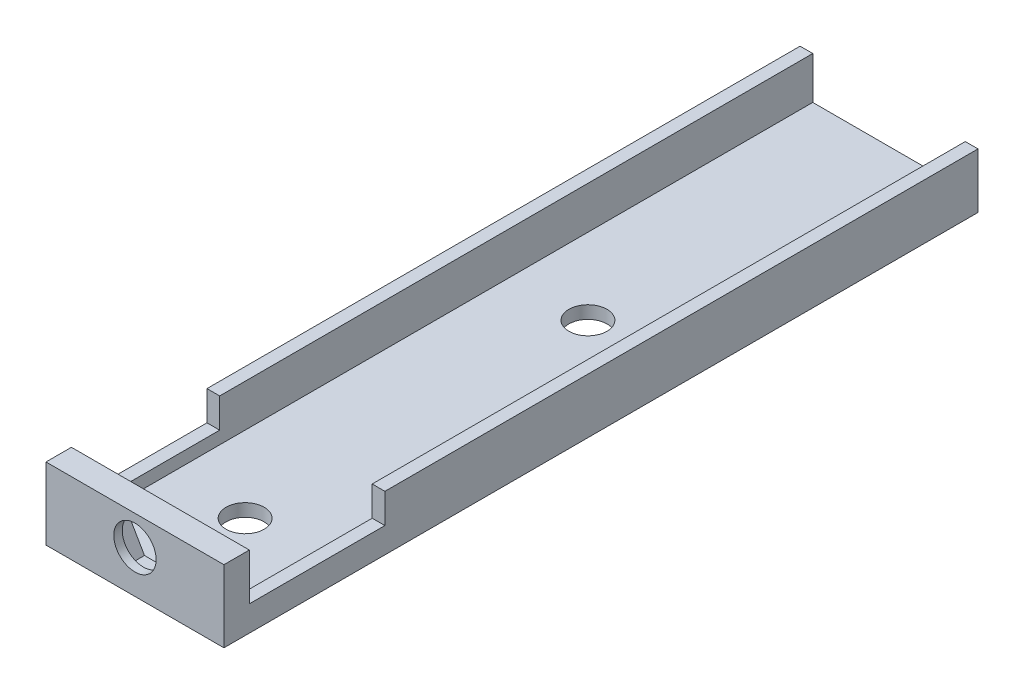
SolidWorks part; units mm, degrees
ref_plane "Front Plane" through (0, 0, 0) normal (0, 0, 1) x (1, 0, 0)
ref_plane "Top Plane" through (0, 0, 0) normal (0, 1, 0) x (1, 0, 0)
ref_plane "Right Plane" through (0, 0, 0) normal (1, 0, 0) x (0, 0, -1)
sketch "Sketch1" plane through (0, 0, 0) normal (0, 0, 1) x (1, 0, 0)
  line L0 (0, 0) -> (0, 13)
  line L1 (0, 13) -> (3, 13)
  line L2 (3, 13) -> (3, 3)
  line L3 (3, 3) -> (39, 3)
  line L4 (39, 3) -> (39, 13)
  line L5 (39, 13) -> (42, 13)
  line L6 (42, 13) -> (42, 0)
  line L7 (42, 0) -> (0, 0)
  line L8 (3, 3) -> (3, 0) construction
  dimension "D1" = 36
  dimension "D2" = 10
  dimension "D3" = 3
extrude "Boss-Extrude1" add sketch "Sketch1" along normal blind 140
sketch "Sketch2" plane through (0, 0, 140) normal (0, 0, 1) x (1, 0, 0)
  line L0 (0, 0) -> (42, 0)
  line L1 (42, 0) -> (42, 6)
  line L2 (42, 0) -> (42, 13) construction
  line L3 (42, 6) -> (39, 6)
  line L4 (39, 13) -> (39, 3) construction
  line L5 (39, 6) -> (39, 3)
  line L6 (39, 3) -> (3, 3)
  line L7 (3, 3) -> (3, 6)
  line L8 (3, 3) -> (3, 13) construction
  line L9 (3, 6) -> (0, 6)
  line L10 (0, 13) -> (0, 0) construction
  line L11 (0, 6) -> (0, 0)
  dimension "D1" = 3
extrude "Boss-Extrude2" add sketch "Sketch2" along normal blind 36
sketch "Sketch3" plane through (0, 0, 176) normal (0, 0, 1) x (1, 0, 0)
  line L0 (21, 10) -> (21, 17) construction
  line L1 (0, 0) -> (42, 0)
  line L2 (0, 0) -> (0, 17)
  line L3 (0, 17) -> (42, 17)
  line L4 (42, 0) -> (42, 17)
  line L5 (21, 10) -> (0, 10) construction
  line L6 (39, 3) -> (3, 3) construction
  line L8 (28.5056, 10) -> (24.7528, 16.5)
  line L9 (24.7528, 16.5) -> (17.2472, 16.5)
  line L10 (17.2472, 16.5) -> (13.4944, 10)
  line L11 (13.4944, 10) -> (17.2472, 3.5)
  line L12 (17.2472, 3.5) -> (24.7528, 3.5)
  line L13 (24.7528, 3.5) -> (28.5056, 10)
  circle A0 centre (21, 10) radius 5
  circle A1 centre (21, 10) radius 6.5 construction
  point P11 (0, 0)
  line M7 (0, 6) -> (0, 0)
  line M8 (0, 0) -> (42, 0)
  line M9 (42, 0) -> (42, 6)
  line M10 (42, 6) -> (39, 6)
  line M11 (39, 6) -> (39, 3)
  line M12 (39, 3) -> (3, 3)
  line M13 (3, 3) -> (3, 6)
  line M14 (3, 6) -> (0, 6)
  dimension "D1" = 10
  dimension "D2" = 17
  dimension "D3" = 13
extrude "Boss-Extrude3" add sketch "Sketch3" against normal blind 4 contours L4 L3 L2 L13 L12 L11 L10 L9 L8 M10 M14 M13 M12 M11 region at (0.4427, 11.5, 176)
extrude "Boss-Extrude4" add sketch "Sketch3<3>" along normal blind 2 contours M14 M7 M8 M9 M10 M11 M12 M13 | L4 L3 L2 L13 L12 L11 L10 L9 L8 M10 M14 M13 M12 M11 | L12 L13 L8 L9 L10 L11 A0 region at (21, 1.875, 176) region at (0.4427, 11.5, 176) region at (26.4572, 6.8493, 176)
sketch "Sketch3<3>" plane through (0, 0, 176) normal (0, 0, 1) x (1, 0, 0) same geometry as "Sketch3"
sketch "Sketch4" plane through (0, 3, 0) normal (0, 1, 0) x (1, 0, 0)
  line L1 (21, -152) -> (21, -71.075) construction
  line L2 (3, -172) -> (3, 0) construction
  line L3 (39, -172) -> (39, 0) construction
  line L4 (39, -172) -> (3, -172) construction
  circle A0 centre (21, -152) radius 4.5
  circle A1 centre (21, -71.075) radius 4.5
  dimension "D2" = 9
  dimension "D1" = 20
  dimension "D3" = 80.925
extrude "Cut-Extrude1" cut sketch "Sketch4" against normal through all
